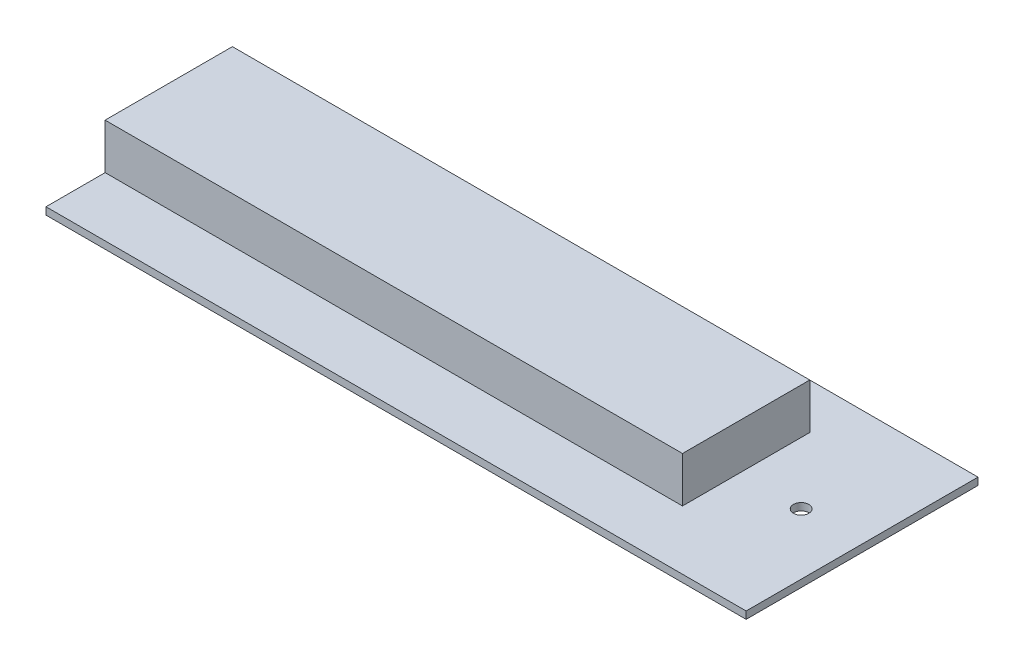
SolidWorks part; units mm, degrees
ref_plane "Front Plane" through (0, 0, 0) normal (0, 0, 1) x (1, 0, 0)
ref_plane "Top Plane" through (0, 0, 0) normal (0, 1, 0) x (1, 0, 0)
ref_plane "Right Plane" through (0, 0, 0) normal (1, 0, 0) x (0, 0, -1)
sketch "Sketch1" plane through (0, 0, 0) normal (0, 1, 0) x (1, 0, 0)
  line L0 (0, 25.5) -> (154, 25.5) construction
  line L1 (0, 0) -> (154, 0)
  line L2 (0, 0) -> (0, 51)
  line L3 (0, 51) -> (154, 51)
  line L4 (154, 0) -> (154, 51)
  line L5 (77, 51) -> (77, 0) construction
  circle A0 centre (77, 25.5) radius 1.7
  circle A1 centre (13.4, 25.5) radius 1.7
  circle A2 centre (140.6, 25.5) radius 1.7
  dimension "D4" = 3.4
  dimension "D1" = 154
  dimension "D2" = 51
  dimension "D3" = 13.4
extrude "Boss-Extrude1" add sketch "Sketch1" along normal blind 1.6
sketch "Sketch2" plane through (0, 1.6, 0) normal (0, 1, 0) x (1, 0, 0)
  line L0 (0, 13) -> (127, 13)
  line L1 (0, 51) -> (0, 0) construction
  line L2 (127, 13) -> (127, 41)
  line L3 (127, 41) -> (0, 41)
  line L4 (0, 41) -> (0, 13)
  line L5 (154, 0) -> (154, 51) construction
  line L6 (154, 51) -> (0, 51) construction
  line L7 (0, 0) -> (154, 0) construction
  dimension "D1" = 27
  dimension "D2" = 10
  dimension "D3" = 13
extrude "Boss-Extrude2" add sketch "Sketch2" along normal blind 10
